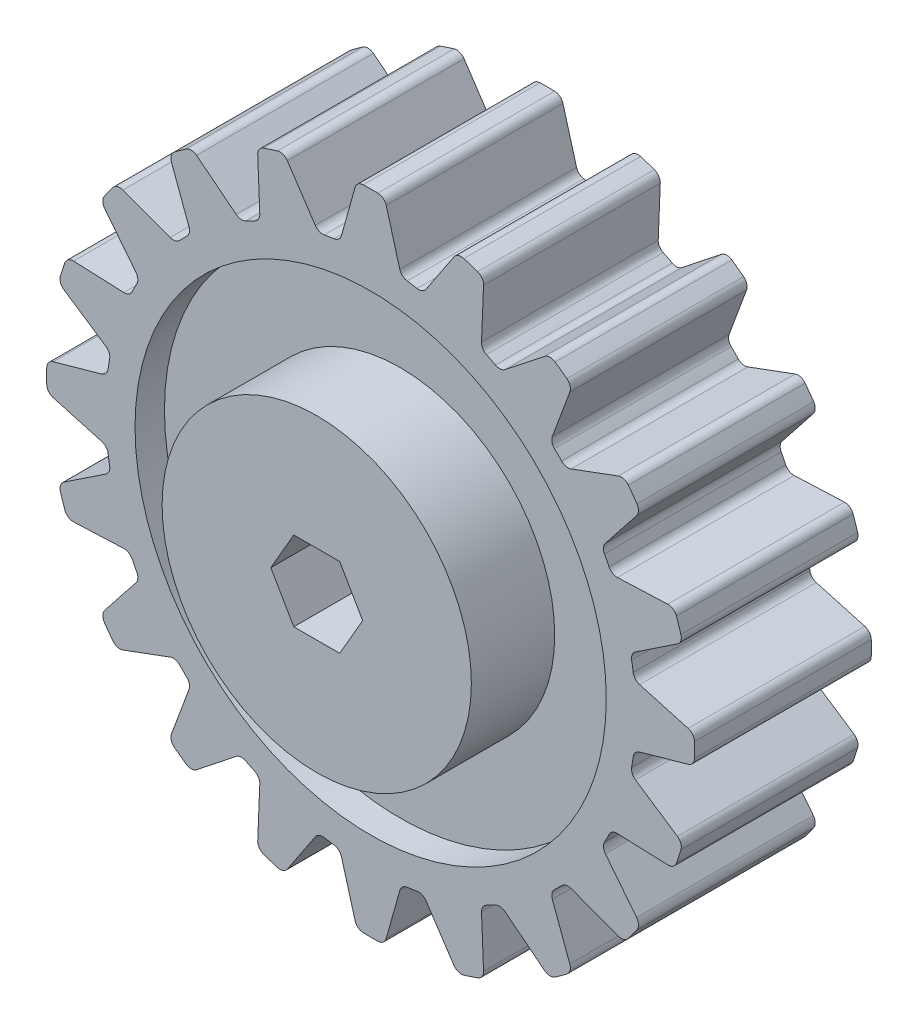
SolidWorks part; units mm, degrees
ref_plane "Front Plane" through (0, 0, 0) normal (0, 0, 1) x (1, 0, 0)
ref_plane "Top Plane" through (0, 0, 0) normal (0, 1, 0) x (1, 0, 0)
ref_plane "Right Plane" through (0, 0, 0) normal (1, 0, 0) x (0, 0, -1)
sketch "Sketch1" plane through (0, 0, 0) normal (0, 0, 1) x (1, 0, 0)
  circle A2 centre (0, 0) radius 9
  dimension "Blank diameter" = 18
extrude "Body" add sketch "Sketch1" against normal blind 6
sketch "Sketch2" plane through (0, 0, 0) normal (0, 0, 1) x (1, 0, 0)
  line L0 (0, 16.3446) -> (0, 3.6554) construction
  line L1 (-0.755, 9.9715) -> (-1.0446, 8.9392)
  line L2 (-0.755, 9.9715) -> (-0.4693, 10.99)
  line L3 (0.755, 9.9715) -> (1.0446, 8.9392)
  line L4 (0.755, 9.9715) -> (0.4693, 10.99)
  line L5 (0, 0) -> (-3.338, 44.0862) construction
  line L6 (0, 0) -> (3.224, 42.5807) construction
  arc A0 (0.4693, 10.99) -> (-0.4693, 10.99) centre (0, 0) ccw
  arc A1 (0.755, 9.9715) -> (-0.755, 9.9715) centre (0, 0) ccw construction
  arc A2 (1.0446, 8.9392) -> (-1.0446, 8.9392) centre (0, 0) ccw
  point P1 (0, 10)
  dimension "D2" = 20
  dimension "D3" = 20
  dimension "Full diameter" = 22
  dimension "Pitch diameter" = 20
  dimension "Blank diameter" = 18
  dimension "Tooth width PCD" = 1.51
extrude "Tooth" add sketch "Sketch2" against normal blind 6
fillet "Tooth Fillet" radius 0.3 4 edges at (-0.4693, 10.99, -3) (-1.0446, 8.9392, -3) (0.4693, 10.99, -3) (1.0446, 8.9392, -3)
pattern_circular "Tooth Pattern" count 20 over 360 about axis through (0, 0, 0) along (0, 0, 1) of "Tooth", "Tooth Fillet"
ref_axis "Axis1" through (0, 0, 0) along (0, 0, -1)
sketch "Sketch3" plane through (0, 0, 0) normal (0, 0, 1) x (1, 0, 0)
  circle A0 centre (0, 0) radius 5.25
  circle A1 centre (0, 0) radius 8
  dimension "Plastic boss" = 10.5
  dimension "Resses" = 16
extrude "Resses1" cut sketch "Sketch3" against normal blind 1
sketch "Sketch4" plane through (0, 0, -6) normal (0, 0, -1) x (-1, 0, 0)
  circle A0 centre (0, 0) radius 8
  circle A1 centre (0, 0) radius 5.25
  dimension "Plastic boss" = 10.5
  dimension "Resses" = 16
extrude "Resses2" cut sketch "Sketch4" against normal blind 1
sketch "Sketch5" plane through (0, 0, -6) normal (0, 0, -1) x (-1, 0, 0)
  circle A0 centre (0, 0) radius 5
  dimension "D1" = 10
extrude "Brass boss" [suppressed] add sketch "Sketch5" along normal blind 5.7
sketch "Sketch6" [suppressed] plane through (0, 0, -11.7) normal (0, 0, -1) x (-1, 0, 0)
  circle A0 centre (0, 0) radius 2
  dimension "D1" = 4
extrude "Bore" [suppressed] cut sketch "Sketch6" against normal through all
sketch "Sketch7" plane through (0, 0, 0) normal (0, 1, 0) x (1, 0, 0)
  circle A0 centre (0, 8.8626) radius 1
  dimension "D1" = 2
extrude "Grub screw" [suppressed] cut sketch "Sketch7" against normal through all
sketch "Sketch8" plane through (0, 0, -5) normal (0, 0, -1) x (-1, 0, 0)
  circle A0 centre (-0.8321, 10.5608) radius 1.8434
extrude "Extrude1" [suppressed] add sketch "Sketch8" along normal blind 5
sketch "Sketch9" plane through (0, 0, -6) normal (0, 0, -1) x (-1, 0, 0)
  circle A0 centre (0, 0) radius 5.25 construction
  circle A1 centre (0, 0) radius 5.25
extrude "Boss-Extrude1" add sketch "Sketch9" along normal blind 1.83 and the other way blind 7.83
sketch "Sketch10" plane through (0, 0, -7.83) normal (0, 0, -1) x (-1, 0, 0)
  line L1 (0.7794, 1.35) -> (-0.7794, 1.35)
  line L2 (-0.7794, 1.35) -> (-1.5588, 0)
  line L3 (-1.5588, 0) -> (-0.7794, -1.35)
  line L4 (-0.7794, -1.35) -> (0.7794, -1.35)
  line L5 (0.7794, -1.35) -> (1.5588, 0)
  line L6 (1.5588, 0) -> (0.7794, 1.35)
  circle A0 centre (0, 0) radius 1.35 construction
  point P1 (1.3652, 0.7525)
  point P10 (-1.5588, 0)
  dimension "D1" = 2.7
extrude "Cut-Extrude1" cut sketch "Sketch10" against normal through all
